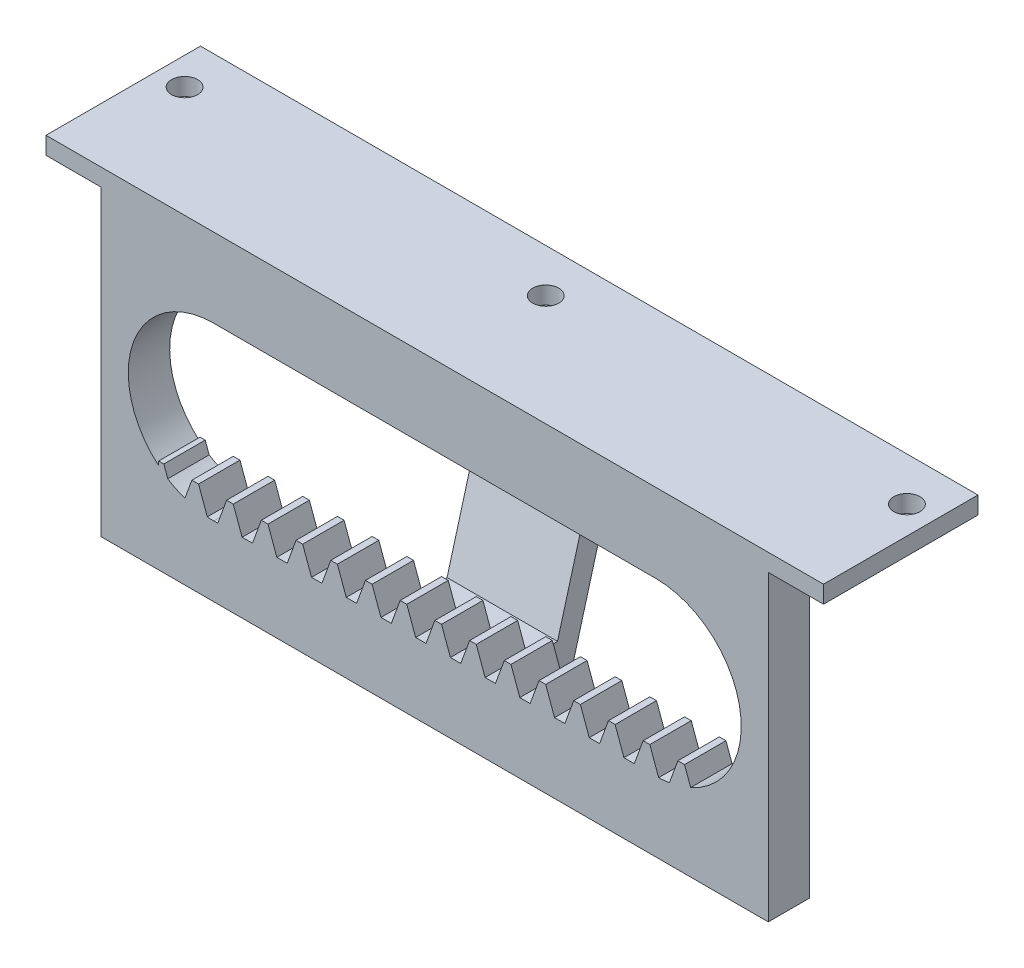
SolidWorks part; units mm, degrees
material "Nylon 101"
ref_plane "Front Plane" through (0, 0, 0) normal (0, 0, 1) x (1, 0, 0)
ref_plane "Top Plane" through (0, 0, 0) normal (0, 1, 0) x (1, 0, 0)
ref_plane "Right Plane" through (0, 0, 0) normal (1, 0, 0) x (0, 0, -1)
sketch "Sketch1" plane through (0, 0, 0) normal (0, 1, 0) x (1, 0, 0)
  line L0 (0, 0) -> (0, 4.7625)
  line L1 (0, 4.7625) -> (63.5, 4.7625)
  line L2 (63.5, 4.7625) -> (63.5, 0)
  line L3 (63.5, 0) -> (0, 0)
  dimension "D1" = 4.7625
  dimension "D2" = 63.5
extrude "Boss-Extrude1" add sketch "Sketch1" along normal blind 4.5
sketch "Sketch2" plane through (0, 0, 0) normal (0, 0, 1) x (1, 0, 0)
  line L0 (0, 3.2275) -> (63.5, 3.2275) construction
  line L1 (0, 4.5) -> (0, 0) construction
  line L2 (63.5, 4.5) -> (63.5, 0) construction
  line L3 (0, 1.7035) -> (63.5, 1.7035) construction
  line L4 (0, 4.5) -> (63.5, 4.5) construction
  line L5 (0, 4.5) -> (0.5952, 4.5) construction
  line L6 (0.5952, 4.5) -> (1.613, 1.7035)
  line L7 (1.613, 1.7035) -> (2.2082, 1.7035)
  line L8 (2.8034, 1.7035) -> (3.8212, 4.5)
  line L9 (3.8212, 4.5) -> (4.4164, 4.5) construction
  line L10 (2.2082, 1.7035) -> (2.8034, 1.7035)
  line L11 (0.5952, 4.5) -> (3.8212, 4.5)
  line L12 (4.5868, 4.5) -> (5.6047, 1.7035)
  line L13 (5.6047, 1.7035) -> (6.1999, 1.7035)
  line L14 (6.795, 1.7035) -> (7.8129, 4.5)
  line L15 (6.1999, 1.7035) -> (6.795, 1.7035)
  line L16 (4.5868, 4.5) -> (7.8129, 4.5)
  line L17 (3.9917, 4.5) -> (4.5868, 4.5) construction
  line L18 (7.8129, 4.5) -> (8.4081, 4.5) construction
  line L19 (8.5785, 4.5) -> (9.5964, 1.7035)
  line L20 (9.5964, 1.7035) -> (10.1915, 1.7035)
  line L21 (10.7867, 1.7035) -> (11.8046, 4.5)
  line L22 (10.1915, 1.7035) -> (10.7867, 1.7035)
  line L23 (8.5785, 4.5) -> (11.8046, 4.5)
  line L24 (7.9834, 4.5) -> (8.5785, 4.5) construction
  line L25 (11.8046, 4.5) -> (12.3997, 4.5) construction
  line L26 (12.5702, 4.5) -> (13.5881, 1.7035)
  line L27 (13.5881, 1.7035) -> (14.1832, 1.7035)
  line L28 (14.7784, 1.7035) -> (15.7962, 4.5)
  line L29 (14.1832, 1.7035) -> (14.7784, 1.7035)
  line L30 (12.5702, 4.5) -> (15.7962, 4.5)
  line L31 (11.975, 4.5) -> (12.5702, 4.5) construction
  line L32 (15.7962, 4.5) -> (16.3914, 4.5) construction
  line L33 (16.5619, 4.5) -> (17.5797, 1.7035)
  line L34 (17.5797, 1.7035) -> (18.1749, 1.7035)
  line L35 (18.7701, 1.7035) -> (19.7879, 4.5)
  line L36 (18.1749, 1.7035) -> (18.7701, 1.7035)
  line L37 (16.5619, 4.5) -> (19.7879, 4.5)
  line L38 (15.9667, 4.5) -> (16.5619, 4.5) construction
  line L39 (19.7879, 4.5) -> (20.3831, 4.5) construction
  line L40 (20.5535, 4.5) -> (21.5714, 1.7035)
  line L41 (21.5714, 1.7035) -> (22.1666, 1.7035)
  line L42 (22.7617, 1.7035) -> (23.7796, 4.5)
  line L43 (22.1666, 1.7035) -> (22.7617, 1.7035)
  line L44 (20.5535, 4.5) -> (23.7796, 4.5)
  line L45 (19.9584, 4.5) -> (20.5535, 4.5) construction
  line L46 (23.7796, 4.5) -> (24.3748, 4.5) construction
  line L47 (24.5452, 4.5) -> (25.5631, 1.7035)
  line L48 (25.5631, 1.7035) -> (26.1582, 1.7035)
  line L49 (26.7534, 1.7035) -> (27.7713, 4.5)
  line L50 (26.1582, 1.7035) -> (26.7534, 1.7035)
  line L51 (24.5452, 4.5) -> (27.7713, 4.5)
  line L52 (23.9501, 4.5) -> (24.5452, 4.5) construction
  line L53 (27.7713, 4.5) -> (28.3664, 4.5) construction
  line L54 (28.5369, 4.5) -> (29.5548, 1.7035)
  line L55 (29.5548, 1.7035) -> (30.1499, 1.7035)
  line L56 (30.7451, 1.7035) -> (31.763, 4.5)
  line L57 (30.1499, 1.7035) -> (30.7451, 1.7035)
  line L58 (28.5369, 4.5) -> (31.763, 4.5)
  line L59 (27.9417, 4.5) -> (28.5369, 4.5) construction
  line L60 (31.763, 4.5) -> (32.3581, 4.5) construction
  line L61 (32.5286, 4.5) -> (33.5464, 1.7035)
  line L62 (33.5464, 1.7035) -> (34.1416, 1.7035)
  line L63 (34.7368, 1.7035) -> (35.7546, 4.5)
  line L64 (34.1416, 1.7035) -> (34.7368, 1.7035)
  line L65 (32.5286, 4.5) -> (35.7546, 4.5)
  line L66 (31.9334, 4.5) -> (32.5286, 4.5) construction
  line L67 (35.7546, 4.5) -> (36.3498, 4.5) construction
  line L68 (36.5203, 4.5) -> (37.5381, 1.7035)
  line L69 (37.5381, 1.7035) -> (38.1333, 1.7035)
  line L70 (38.7284, 1.7035) -> (39.7463, 4.5)
  line L71 (38.1333, 1.7035) -> (38.7284, 1.7035)
  line L72 (36.5203, 4.5) -> (39.7463, 4.5)
  line L73 (35.9251, 4.5) -> (36.5203, 4.5) construction
  line L74 (39.7463, 4.5) -> (40.3415, 4.5) construction
  line L75 (40.5119, 4.5) -> (41.5298, 1.7035)
  line L76 (41.5298, 1.7035) -> (42.125, 1.7035)
  line L77 (42.7201, 1.7035) -> (43.738, 4.5)
  line L78 (42.125, 1.7035) -> (42.7201, 1.7035)
  line L79 (40.5119, 4.5) -> (43.738, 4.5)
  line L80 (39.9168, 4.5) -> (40.5119, 4.5) construction
  line L81 (43.738, 4.5) -> (44.3331, 4.5) construction
  line L82 (44.5036, 4.5) -> (45.5215, 1.7035)
  line L83 (45.5215, 1.7035) -> (46.1166, 1.7035)
  line L84 (46.7118, 1.7035) -> (47.7297, 4.5)
  line L85 (46.1166, 1.7035) -> (46.7118, 1.7035)
  line L86 (44.5036, 4.5) -> (47.7297, 4.5)
  line L87 (43.9084, 4.5) -> (44.5036, 4.5) construction
  line L88 (47.7297, 4.5) -> (48.3248, 4.5) construction
  line L89 (48.4953, 4.5) -> (49.5131, 1.7035)
  line L90 (49.5131, 1.7035) -> (50.1083, 1.7035)
  line L91 (50.7035, 1.7035) -> (51.7213, 4.5)
  line L92 (50.1083, 1.7035) -> (50.7035, 1.7035)
  line L93 (48.4953, 4.5) -> (51.7213, 4.5)
  line L94 (47.9001, 4.5) -> (48.4953, 4.5) construction
  line L95 (51.7213, 4.5) -> (52.3165, 4.5) construction
  line L96 (52.487, 4.5) -> (53.5048, 1.7035)
  line L97 (53.5048, 1.7035) -> (54.1, 1.7035)
  line L98 (54.6952, 1.7035) -> (55.713, 4.5)
  line L99 (54.1, 1.7035) -> (54.6952, 1.7035)
  line L100 (52.487, 4.5) -> (55.713, 4.5)
  line L101 (51.8918, 4.5) -> (52.487, 4.5) construction
  line L102 (55.713, 4.5) -> (56.3082, 4.5) construction
  line L103 (56.4786, 4.5) -> (57.4965, 1.7035)
  line L104 (57.4965, 1.7035) -> (58.0917, 1.7035)
  line L105 (58.6868, 1.7035) -> (59.7047, 4.5)
  line L106 (58.0917, 1.7035) -> (58.6868, 1.7035)
  line L107 (56.4786, 4.5) -> (59.7047, 4.5)
  line L108 (55.8835, 4.5) -> (56.4786, 4.5) construction
  line L109 (59.7047, 4.5) -> (60.2999, 4.5) construction
  line L110 (60.4703, 4.5) -> (61.4882, 1.7035)
  line L111 (61.4882, 1.7035) -> (62.0833, 1.7035)
  line L112 (62.6785, 1.7035) -> (63.6964, 4.5)
  line L113 (62.0833, 1.7035) -> (62.6785, 1.7035)
  line L114 (60.4703, 4.5) -> (63.6964, 4.5)
  line L115 (59.8751, 4.5) -> (60.4703, 4.5) construction
  line L116 (63.6964, 4.5) -> (64.2915, 4.5) construction
  line L117 (64.462, 4.5) -> (65.4798, 1.7035)
  line L118 (65.4798, 1.7035) -> (66.075, 1.7035)
  line L119 (66.6702, 1.7035) -> (67.688, 4.5)
  line L120 (66.075, 1.7035) -> (66.6702, 1.7035)
  line L121 (64.462, 4.5) -> (67.688, 4.5)
  line L122 (63.8668, 4.5) -> (64.462, 4.5) construction
  line L123 (67.688, 4.5) -> (68.2832, 4.5) construction
  line L124 (68.4537, 4.5) -> (69.4715, 1.7035)
  line L125 (69.4715, 1.7035) -> (70.0667, 1.7035)
  line L126 (70.6619, 1.7035) -> (71.6797, 4.5)
  line L127 (70.0667, 1.7035) -> (70.6619, 1.7035)
  line L128 (68.4537, 4.5) -> (71.6797, 4.5)
  line L129 (67.8585, 4.5) -> (68.4537, 4.5) construction
  line L130 (71.6797, 4.5) -> (72.2749, 4.5) construction
  line L131 (72.4453, 4.5) -> (73.4632, 1.7035)
  line L132 (73.4632, 1.7035) -> (74.0584, 1.7035)
  line L133 (74.6535, 1.7035) -> (75.6714, 4.5)
  line L134 (74.0584, 1.7035) -> (74.6535, 1.7035)
  line L135 (72.4453, 4.5) -> (75.6714, 4.5)
  line L136 (71.8502, 4.5) -> (72.4453, 4.5) construction
  line L137 (75.6714, 4.5) -> (76.2666, 4.5) construction
  line L138 (76.437, 4.5) -> (77.4549, 1.7035)
  line L139 (77.4549, 1.7035) -> (78.05, 1.7035)
  line L140 (78.6452, 1.7035) -> (79.6631, 4.5)
  line L141 (78.05, 1.7035) -> (78.6452, 1.7035)
  line L142 (76.437, 4.5) -> (79.6631, 4.5)
  line L143 (75.8418, 4.5) -> (76.437, 4.5) construction
  line L144 (79.6631, 4.5) -> (80.2582, 4.5) construction
  line L145 (80.4287, 4.5) -> (81.4465, 1.7035)
  line L146 (81.4465, 1.7035) -> (82.0417, 1.7035)
  line L147 (82.6369, 1.7035) -> (83.6547, 4.5)
  line L148 (82.0417, 1.7035) -> (82.6369, 1.7035)
  line L149 (80.4287, 4.5) -> (83.6547, 4.5)
  line L150 (79.8335, 4.5) -> (80.4287, 4.5) construction
  line L151 (83.6547, 4.5) -> (84.2499, 4.5) construction
  line L152 (84.4204, 4.5) -> (85.4382, 1.7035)
  line L153 (85.4382, 1.7035) -> (86.0334, 1.7035)
  line L154 (86.6286, 1.7035) -> (87.6464, 4.5)
  line L155 (86.0334, 1.7035) -> (86.6286, 1.7035)
  line L156 (84.4204, 4.5) -> (87.6464, 4.5)
  line L157 (83.8252, 4.5) -> (84.4204, 4.5) construction
  line L158 (87.6464, 4.5) -> (88.2416, 4.5) construction
  line L159 (88.412, 4.5) -> (89.4299, 1.7035)
  line L160 (89.4299, 1.7035) -> (90.0251, 1.7035)
  line L161 (90.6202, 1.7035) -> (91.6381, 4.5)
  line L162 (90.0251, 1.7035) -> (90.6202, 1.7035)
  line L163 (88.412, 4.5) -> (91.6381, 4.5)
  line L164 (87.8169, 4.5) -> (88.412, 4.5) construction
  line L165 (91.6381, 4.5) -> (92.2333, 4.5) construction
  line L166 (92.4037, 4.5) -> (93.4216, 1.7035)
  line L167 (93.4216, 1.7035) -> (94.0167, 1.7035)
  line L168 (94.6119, 1.7035) -> (95.6298, 4.5)
  line L169 (94.0167, 1.7035) -> (94.6119, 1.7035)
  line L170 (92.4037, 4.5) -> (95.6298, 4.5)
  line L171 (91.8086, 4.5) -> (92.4037, 4.5) construction
  line L172 (95.6298, 4.5) -> (96.2249, 4.5) construction
  line L173 (96.3954, 4.5) -> (97.4133, 1.7035)
  line L174 (97.4133, 1.7035) -> (98.0084, 1.7035)
  line L175 (98.6036, 1.7035) -> (99.6214, 4.5)
  line L176 (98.0084, 1.7035) -> (98.6036, 1.7035)
  line L177 (96.3954, 4.5) -> (99.6214, 4.5)
  line L178 (95.8002, 4.5) -> (96.3954, 4.5) construction
  line L179 (99.6214, 4.5) -> (100.2166, 4.5) construction
  line L180 (100.3871, 4.5) -> (101.4049, 1.7035)
  line L181 (101.4049, 1.7035) -> (102.0001, 1.7035)
  line L182 (102.5953, 1.7035) -> (103.6131, 4.5)
  line L183 (102.0001, 1.7035) -> (102.5953, 1.7035)
  line L184 (100.3871, 4.5) -> (103.6131, 4.5)
  line L185 (99.7919, 4.5) -> (100.3871, 4.5) construction
  line L186 (103.6131, 4.5) -> (104.2083, 4.5) construction
  line L187 (104.3787, 4.5) -> (105.3966, 1.7035)
  line L188 (105.3966, 1.7035) -> (105.9918, 1.7035)
  line L189 (106.5869, 1.7035) -> (107.6048, 4.5)
  line L190 (105.9918, 1.7035) -> (106.5869, 1.7035)
  line L191 (104.3787, 4.5) -> (107.6048, 4.5)
  line L192 (103.7836, 4.5) -> (104.3787, 4.5) construction
  line L193 (107.6048, 4.5) -> (108.2, 4.5) construction
  line L194 (108.3704, 4.5) -> (109.3883, 1.7035)
  line L195 (109.3883, 1.7035) -> (109.9835, 1.7035)
  line L196 (110.5786, 1.7035) -> (111.5965, 4.5)
  line L197 (109.9835, 1.7035) -> (110.5786, 1.7035)
  line L198 (108.3704, 4.5) -> (111.5965, 4.5)
  line L199 (107.7753, 4.5) -> (108.3704, 4.5) construction
  line L200 (111.5965, 4.5) -> (112.1916, 4.5) construction
  line L201 (112.3621, 4.5) -> (113.38, 1.7035)
  line L202 (113.38, 1.7035) -> (113.9751, 1.7035)
  line L203 (114.5703, 1.7035) -> (115.5882, 4.5)
  line L204 (113.9751, 1.7035) -> (114.5703, 1.7035)
  line L205 (112.3621, 4.5) -> (115.5882, 4.5)
  line L206 (111.7669, 4.5) -> (112.3621, 4.5) construction
  line L207 (115.5882, 4.5) -> (116.1833, 4.5) construction
  line L208 (116.3538, 4.5) -> (117.3716, 1.7035)
  line L209 (117.3716, 1.7035) -> (117.9668, 1.7035)
  line L210 (118.562, 1.7035) -> (119.5798, 4.5)
  line L211 (117.9668, 1.7035) -> (118.562, 1.7035)
  line L212 (116.3538, 4.5) -> (119.5798, 4.5)
  line L213 (115.7586, 4.5) -> (116.3538, 4.5) construction
  line L214 (119.5798, 4.5) -> (120.175, 4.5) construction
  line L215 (120.3455, 4.5) -> (121.3633, 1.7035)
  line L216 (121.3633, 1.7035) -> (121.9585, 1.7035)
  line L217 (122.5536, 1.7035) -> (123.5715, 4.5)
  line L218 (121.9585, 1.7035) -> (122.5536, 1.7035)
  line L219 (120.3455, 4.5) -> (123.5715, 4.5)
  line L220 (119.7503, 4.5) -> (120.3455, 4.5) construction
  line L221 (123.5715, 4.5) -> (124.1667, 4.5) construction
  line L222 (124.3371, 4.5) -> (125.355, 1.7035)
  line L223 (125.355, 1.7035) -> (125.9502, 1.7035)
  line L224 (126.5453, 1.7035) -> (127.5632, 4.5)
  line L225 (125.9502, 1.7035) -> (126.5453, 1.7035)
  line L226 (124.3371, 4.5) -> (127.5632, 4.5)
  line L227 (123.742, 4.5) -> (124.3371, 4.5) construction
  line L228 (127.5632, 4.5) -> (128.1583, 4.5) construction
  line L229 (128.3288, 4.5) -> (129.3467, 1.7035)
  line L230 (129.3467, 1.7035) -> (129.9418, 1.7035)
  line L231 (130.537, 1.7035) -> (131.5549, 4.5)
  line L232 (129.9418, 1.7035) -> (130.537, 1.7035)
  line L233 (128.3288, 4.5) -> (131.5549, 4.5)
  line L234 (127.7336, 4.5) -> (128.3288, 4.5) construction
  line L235 (131.5549, 4.5) -> (132.15, 4.5) construction
  line L236 (132.3205, 4.5) -> (133.3383, 1.7035)
  line L237 (133.3383, 1.7035) -> (133.9335, 1.7035)
  line L238 (134.5287, 1.7035) -> (135.5465, 4.5)
  line L239 (133.9335, 1.7035) -> (134.5287, 1.7035)
  line L240 (132.3205, 4.5) -> (135.5465, 4.5)
  line L241 (131.7253, 4.5) -> (132.3205, 4.5) construction
  line L242 (135.5465, 4.5) -> (136.1417, 4.5) construction
  line L243 (136.3122, 4.5) -> (137.33, 1.7035)
  line L244 (137.33, 1.7035) -> (137.9252, 1.7035)
  line L245 (138.5204, 1.7035) -> (139.5382, 4.5)
  line L246 (137.9252, 1.7035) -> (138.5204, 1.7035)
  line L247 (136.3122, 4.5) -> (139.5382, 4.5)
  line L248 (135.717, 4.5) -> (136.3122, 4.5) construction
  line L249 (139.5382, 4.5) -> (140.1334, 4.5) construction
  line L250 (140.3038, 4.5) -> (141.3217, 1.7035)
  line L251 (141.3217, 1.7035) -> (141.9169, 1.7035)
  line L252 (142.512, 1.7035) -> (143.5299, 4.5)
  line L253 (141.9169, 1.7035) -> (142.512, 1.7035)
  line L254 (140.3038, 4.5) -> (143.5299, 4.5)
  line L255 (139.7087, 4.5) -> (140.3038, 4.5) construction
  line L256 (143.5299, 4.5) -> (144.1251, 4.5) construction
  line L257 (144.2955, 4.5) -> (145.3134, 1.7035)
  line L258 (145.3134, 1.7035) -> (145.9085, 1.7035)
  line L259 (146.5037, 1.7035) -> (147.5216, 4.5)
  line L260 (145.9085, 1.7035) -> (146.5037, 1.7035)
  line L261 (144.2955, 4.5) -> (147.5216, 4.5)
  line L262 (143.7003, 4.5) -> (144.2955, 4.5) construction
  line L263 (147.5216, 4.5) -> (148.1167, 4.5) construction
  line L264 (148.2872, 4.5) -> (149.305, 1.7035)
  line L265 (149.305, 1.7035) -> (149.9002, 1.7035)
  line L266 (150.4954, 1.7035) -> (151.5132, 4.5)
  line L267 (149.9002, 1.7035) -> (150.4954, 1.7035)
  line L268 (148.2872, 4.5) -> (151.5132, 4.5)
  line L269 (147.692, 4.5) -> (148.2872, 4.5) construction
  line L270 (151.5132, 4.5) -> (152.1084, 4.5) construction
  line L271 (152.2789, 4.5) -> (153.2967, 1.7035)
  line L272 (153.2967, 1.7035) -> (153.8919, 1.7035)
  line L273 (154.4871, 1.7035) -> (155.5049, 4.5)
  line L274 (153.8919, 1.7035) -> (154.4871, 1.7035)
  line L275 (152.2789, 4.5) -> (155.5049, 4.5)
  line L276 (151.6837, 4.5) -> (152.2789, 4.5) construction
  line L277 (155.5049, 4.5) -> (156.1001, 4.5) construction
  line L278 (156.2705, 4.5) -> (157.2884, 1.7035)
  line L279 (157.2884, 1.7035) -> (157.8836, 1.7035)
  line L280 (158.4787, 1.7035) -> (159.4966, 4.5)
  line L281 (157.8836, 1.7035) -> (158.4787, 1.7035)
  line L282 (156.2705, 4.5) -> (159.4966, 4.5)
  line L283 (155.6754, 4.5) -> (156.2705, 4.5) construction
  line L284 (159.4966, 4.5) -> (160.0918, 4.5) construction
  line L285 (160.2622, 4.5) -> (161.2801, 1.7035)
  line L286 (161.2801, 1.7035) -> (161.8752, 1.7035)
  line L287 (162.4704, 1.7035) -> (163.4883, 4.5)
  line L288 (161.8752, 1.7035) -> (162.4704, 1.7035)
  line L289 (160.2622, 4.5) -> (163.4883, 4.5)
  line L290 (159.667, 4.5) -> (160.2622, 4.5) construction
  line L291 (163.4883, 4.5) -> (164.0834, 4.5) construction
  line L292 (164.2539, 4.5) -> (165.2718, 1.7035)
  line L293 (165.2718, 1.7035) -> (165.8669, 1.7035)
  line L294 (166.4621, 1.7035) -> (167.4799, 4.5)
  line L295 (165.8669, 1.7035) -> (166.4621, 1.7035)
  line L296 (164.2539, 4.5) -> (167.4799, 4.5)
  line L297 (163.6587, 4.5) -> (164.2539, 4.5) construction
  line L298 (167.4799, 4.5) -> (168.0751, 4.5) construction
  line L299 (168.2456, 4.5) -> (169.2634, 1.7035)
  line L300 (169.2634, 1.7035) -> (169.8586, 1.7035)
  line L301 (170.4538, 1.7035) -> (171.4716, 4.5)
  line L302 (169.8586, 1.7035) -> (170.4538, 1.7035)
  line L303 (168.2456, 4.5) -> (171.4716, 4.5)
  line L304 (167.6504, 4.5) -> (168.2456, 4.5) construction
  line L305 (171.4716, 4.5) -> (172.0668, 4.5) construction
  line L306 (172.2372, 4.5) -> (173.2551, 1.7035)
  line L307 (173.2551, 1.7035) -> (173.8503, 1.7035)
  line L308 (174.4454, 1.7035) -> (175.4633, 4.5)
  line L309 (173.8503, 1.7035) -> (174.4454, 1.7035)
  line L310 (172.2372, 4.5) -> (175.4633, 4.5)
  line L311 (171.6421, 4.5) -> (172.2372, 4.5) construction
  line L312 (175.4633, 4.5) -> (176.0585, 4.5) construction
  line L313 (176.2289, 4.5) -> (177.2468, 1.7035)
  line L314 (177.2468, 1.7035) -> (177.8419, 1.7035)
  line L315 (178.4371, 1.7035) -> (179.455, 4.5)
  line L316 (177.8419, 1.7035) -> (178.4371, 1.7035)
  line L317 (176.2289, 4.5) -> (179.455, 4.5)
  line L318 (175.6338, 4.5) -> (176.2289, 4.5) construction
  line L319 (179.455, 4.5) -> (180.0501, 4.5) construction
  line L320 (180.2206, 4.5) -> (181.2385, 1.7035)
  line L321 (181.2385, 1.7035) -> (181.8336, 1.7035)
  line L322 (182.4288, 1.7035) -> (183.4466, 4.5)
  line L323 (181.8336, 1.7035) -> (182.4288, 1.7035)
  line L324 (180.2206, 4.5) -> (183.4466, 4.5)
  line L325 (179.6254, 4.5) -> (180.2206, 4.5) construction
  line L326 (183.4466, 4.5) -> (184.0418, 4.5) construction
  line L327 (184.2123, 4.5) -> (185.2301, 1.7035)
  line L328 (185.2301, 1.7035) -> (185.8253, 1.7035)
  line L329 (186.4205, 1.7035) -> (187.4383, 4.5)
  line L330 (185.8253, 1.7035) -> (186.4205, 1.7035)
  line L331 (184.2123, 4.5) -> (187.4383, 4.5)
  line L332 (183.6171, 4.5) -> (184.2123, 4.5) construction
  line L333 (187.4383, 4.5) -> (188.0335, 4.5) construction
  line L334 (188.204, 4.5) -> (189.2218, 1.7035)
  line L335 (189.2218, 1.7035) -> (189.817, 1.7035)
  line L336 (190.4121, 1.7035) -> (191.43, 4.5)
  line L337 (189.817, 1.7035) -> (190.4121, 1.7035)
  line L338 (188.204, 4.5) -> (191.43, 4.5)
  line L339 (187.6088, 4.5) -> (188.204, 4.5) construction
  line L340 (191.43, 4.5) -> (192.0252, 4.5) construction
  line L341 (192.1956, 4.5) -> (193.2135, 1.7035)
  line L342 (193.2135, 1.7035) -> (193.8087, 1.7035)
  line L343 (194.4038, 1.7035) -> (195.4217, 4.5)
  line L344 (193.8087, 1.7035) -> (194.4038, 1.7035)
  line L345 (192.1956, 4.5) -> (195.4217, 4.5)
  line L346 (191.6005, 4.5) -> (192.1956, 4.5) construction
  line L347 (195.4217, 4.5) -> (196.0168, 4.5) construction
  line L348 (196.1873, 4.5) -> (197.2052, 1.7035)
  line L349 (197.2052, 1.7035) -> (197.8003, 1.7035)
  line L350 (198.3955, 1.7035) -> (199.4134, 4.5)
  line L351 (197.8003, 1.7035) -> (198.3955, 1.7035)
  line L352 (196.1873, 4.5) -> (199.4134, 4.5)
  line L353 (195.5921, 4.5) -> (196.1873, 4.5) construction
  line L354 (199.4134, 4.5) -> (200.0085, 4.5) construction
  line L355 (200.179, 4.5) -> (201.1968, 1.7035)
  line L356 (201.1968, 1.7035) -> (201.792, 1.7035)
  line L357 (202.3872, 1.7035) -> (203.405, 4.5)
  line L358 (201.792, 1.7035) -> (202.3872, 1.7035)
  line L359 (200.179, 4.5) -> (203.405, 4.5)
  line L360 (199.5838, 4.5) -> (200.179, 4.5) construction
  line L361 (203.405, 4.5) -> (204.0002, 4.5) construction
  line L362 (204.1707, 4.5) -> (205.1885, 1.7035)
  line L363 (205.1885, 1.7035) -> (205.7837, 1.7035)
  line L364 (206.3788, 1.7035) -> (207.3967, 4.5)
  line L365 (205.7837, 1.7035) -> (206.3788, 1.7035)
  line L366 (204.1707, 4.5) -> (207.3967, 4.5)
  line L367 (203.5755, 4.5) -> (204.1707, 4.5) construction
  line L368 (207.3967, 4.5) -> (207.9919, 4.5) construction
  line L369 (208.1623, 4.5) -> (209.1802, 1.7035)
  line L370 (209.1802, 1.7035) -> (209.7754, 1.7035)
  line L371 (210.3705, 1.7035) -> (211.3884, 4.5)
  line L372 (209.7754, 1.7035) -> (210.3705, 1.7035)
  line L373 (208.1623, 4.5) -> (211.3884, 4.5)
  line L374 (207.5672, 4.5) -> (208.1623, 4.5) construction
  line L375 (211.3884, 4.5) -> (211.9835, 4.5) construction
  line L376 (212.154, 4.5) -> (213.1719, 1.7035)
  line L377 (213.1719, 1.7035) -> (213.767, 1.7035)
  line L378 (214.3622, 1.7035) -> (215.3801, 4.5)
  line L379 (213.767, 1.7035) -> (214.3622, 1.7035)
  line L380 (212.154, 4.5) -> (215.3801, 4.5)
  line L381 (211.5588, 4.5) -> (212.154, 4.5) construction
  line L382 (215.3801, 4.5) -> (215.9752, 4.5) construction
  line L383 (216.1457, 4.5) -> (217.1635, 1.7035)
  line L384 (217.1635, 1.7035) -> (217.7587, 1.7035)
  line L385 (218.3539, 1.7035) -> (219.3717, 4.5)
  line L386 (217.7587, 1.7035) -> (218.3539, 1.7035)
  line L387 (216.1457, 4.5) -> (219.3717, 4.5)
  line L388 (215.5505, 4.5) -> (216.1457, 4.5) construction
  line L389 (219.3717, 4.5) -> (219.9669, 4.5) construction
  line L390 (220.1374, 4.5) -> (221.1552, 1.7035)
  line L391 (221.1552, 1.7035) -> (221.7504, 1.7035)
  line L392 (222.3456, 1.7035) -> (223.3634, 4.5)
  line L393 (221.7504, 1.7035) -> (222.3456, 1.7035)
  line L394 (220.1374, 4.5) -> (223.3634, 4.5)
  line L395 (219.5422, 4.5) -> (220.1374, 4.5) construction
  line L396 (223.3634, 4.5) -> (223.9586, 4.5) construction
  line L397 (224.129, 4.5) -> (225.1469, 1.7035)
  line L398 (225.1469, 1.7035) -> (225.7421, 1.7035)
  line L399 (226.3372, 1.7035) -> (227.3551, 4.5)
  line L400 (225.7421, 1.7035) -> (226.3372, 1.7035)
  line L401 (224.129, 4.5) -> (227.3551, 4.5)
  line L402 (223.5339, 4.5) -> (224.129, 4.5) construction
  line L403 (227.3551, 4.5) -> (227.9503, 4.5) construction
  line L404 (228.1207, 4.5) -> (229.1386, 1.7035)
  line L405 (229.1386, 1.7035) -> (229.7337, 1.7035)
  line L406 (230.3289, 1.7035) -> (231.3468, 4.5)
  line L407 (229.7337, 1.7035) -> (230.3289, 1.7035)
  line L408 (228.1207, 4.5) -> (231.3468, 4.5)
  line L409 (227.5255, 4.5) -> (228.1207, 4.5) construction
  line L410 (231.3468, 4.5) -> (231.9419, 4.5) construction
  line L411 (232.1124, 4.5) -> (233.1302, 1.7035)
  line L412 (233.1302, 1.7035) -> (233.7254, 1.7035)
  line L413 (234.3206, 1.7035) -> (235.3384, 4.5)
  line L414 (233.7254, 1.7035) -> (234.3206, 1.7035)
  line L415 (232.1124, 4.5) -> (235.3384, 4.5)
  line L416 (231.5172, 4.5) -> (232.1124, 4.5) construction
  line L417 (235.3384, 4.5) -> (235.9336, 4.5) construction
  line L418 (236.1041, 4.5) -> (237.1219, 1.7035)
  line L419 (237.1219, 1.7035) -> (237.7171, 1.7035)
  line L420 (238.3123, 1.7035) -> (239.3301, 4.5)
  line L421 (237.7171, 1.7035) -> (238.3123, 1.7035)
  line L422 (236.1041, 4.5) -> (239.3301, 4.5)
  line L423 (235.5089, 4.5) -> (236.1041, 4.5) construction
  line L424 (239.3301, 4.5) -> (239.9253, 4.5) construction
  line L425 (240.0957, 4.5) -> (241.1136, 1.7035)
  line L426 (241.1136, 1.7035) -> (241.7088, 1.7035)
  line L427 (242.3039, 1.7035) -> (243.3218, 4.5)
  line L428 (241.7088, 1.7035) -> (242.3039, 1.7035)
  line L429 (240.0957, 4.5) -> (243.3218, 4.5)
  line L430 (239.5006, 4.5) -> (240.0957, 4.5) construction
  line L431 (243.3218, 4.5) -> (243.917, 4.5) construction
  line L432 (244.0874, 4.5) -> (245.1053, 1.7035)
  line L433 (245.1053, 1.7035) -> (245.7004, 1.7035)
  line L434 (246.2956, 1.7035) -> (247.3135, 4.5)
  line L435 (245.7004, 1.7035) -> (246.2956, 1.7035)
  line L436 (244.0874, 4.5) -> (247.3135, 4.5)
  line L437 (243.4923, 4.5) -> (244.0874, 4.5) construction
  line L438 (247.3135, 4.5) -> (247.9086, 4.5) construction
  line L439 (248.0791, 4.5) -> (249.097, 1.7035)
  line L440 (249.097, 1.7035) -> (249.6921, 1.7035)
  line L441 (250.2873, 1.7035) -> (251.3051, 4.5)
  line L442 (249.6921, 1.7035) -> (250.2873, 1.7035)
  line L443 (248.0791, 4.5) -> (251.3051, 4.5)
  line L444 (247.4839, 4.5) -> (248.0791, 4.5) construction
  line L445 (251.3051, 4.5) -> (251.9003, 4.5) construction
  line L446 (252.0708, 4.5) -> (253.0886, 1.7035)
  line L447 (253.0886, 1.7035) -> (253.6838, 1.7035)
  line L448 (254.279, 1.7035) -> (255.2968, 4.5)
  line L449 (253.6838, 1.7035) -> (254.279, 1.7035)
  line L450 (252.0708, 4.5) -> (255.2968, 4.5)
  line L451 (251.4756, 4.5) -> (252.0708, 4.5) construction
  line L452 (255.2968, 4.5) -> (255.892, 4.5) construction
  line L453 (256.0624, 4.5) -> (257.0803, 1.7035)
  line L454 (257.0803, 1.7035) -> (257.6755, 1.7035)
  line L455 (258.2706, 1.7035) -> (259.2885, 4.5)
  line L456 (257.6755, 1.7035) -> (258.2706, 1.7035)
  line L457 (256.0624, 4.5) -> (259.2885, 4.5)
  line L458 (255.4673, 4.5) -> (256.0624, 4.5) construction
  line L459 (259.2885, 4.5) -> (259.8837, 4.5) construction
  line L460 (260.0541, 4.5) -> (261.072, 1.7035)
  line L461 (261.072, 1.7035) -> (261.6671, 1.7035)
  line L462 (262.2623, 1.7035) -> (263.2802, 4.5)
  line L463 (261.6671, 1.7035) -> (262.2623, 1.7035)
  line L464 (260.0541, 4.5) -> (263.2802, 4.5)
  line L465 (259.459, 4.5) -> (260.0541, 4.5) construction
  line L466 (263.2802, 4.5) -> (263.8753, 4.5) construction
  line L467 (264.0458, 4.5) -> (265.0637, 1.7035)
  line L468 (265.0637, 1.7035) -> (265.6588, 1.7035)
  line L469 (266.254, 1.7035) -> (267.2718, 4.5)
  line L470 (265.6588, 1.7035) -> (266.254, 1.7035)
  line L471 (264.0458, 4.5) -> (267.2718, 4.5)
  line L472 (263.4506, 4.5) -> (264.0458, 4.5) construction
  line L473 (267.2718, 4.5) -> (267.867, 4.5) construction
  line L474 (268.0375, 4.5) -> (269.0553, 1.7035)
  line L475 (269.0553, 1.7035) -> (269.6505, 1.7035)
  line L476 (270.2457, 1.7035) -> (271.2635, 4.5)
  line L477 (269.6505, 1.7035) -> (270.2457, 1.7035)
  line L478 (268.0375, 4.5) -> (271.2635, 4.5)
  line L479 (267.4423, 4.5) -> (268.0375, 4.5) construction
  line L480 (271.2635, 4.5) -> (271.8587, 4.5) construction
  line L481 (272.0292, 4.5) -> (273.047, 1.7035)
  line L482 (273.047, 1.7035) -> (273.6422, 1.7035)
  line L483 (274.2373, 1.7035) -> (275.2552, 4.5)
  line L484 (273.6422, 1.7035) -> (274.2373, 1.7035)
  line L485 (272.0292, 4.5) -> (275.2552, 4.5)
  line L486 (271.434, 4.5) -> (272.0292, 4.5) construction
  line L487 (275.2552, 4.5) -> (275.8504, 4.5) construction
  line L488 (276.0208, 4.5) -> (277.0387, 1.7035)
  line L489 (277.0387, 1.7035) -> (277.6339, 1.7035)
  line L490 (278.229, 1.7035) -> (279.2469, 4.5)
  line L491 (277.6339, 1.7035) -> (278.229, 1.7035)
  line L492 (276.0208, 4.5) -> (279.2469, 4.5)
  line L493 (275.4257, 4.5) -> (276.0208, 4.5) construction
  line L494 (279.2469, 4.5) -> (279.842, 4.5) construction
  line L495 (280.0125, 4.5) -> (281.0304, 1.7035)
  line L496 (281.0304, 1.7035) -> (281.6255, 1.7035)
  line L497 (282.2207, 1.7035) -> (283.2386, 4.5)
  line L498 (281.6255, 1.7035) -> (282.2207, 1.7035)
  line L499 (280.0125, 4.5) -> (283.2386, 4.5)
  line L500 (279.4173, 4.5) -> (280.0125, 4.5) construction
  line L501 (283.2386, 4.5) -> (283.8337, 4.5) construction
  line L502 (284.0042, 4.5) -> (285.022, 1.7035)
  line L503 (285.022, 1.7035) -> (285.6172, 1.7035)
  line L504 (286.2124, 1.7035) -> (287.2302, 4.5)
  line L505 (285.6172, 1.7035) -> (286.2124, 1.7035)
  line L506 (284.0042, 4.5) -> (287.2302, 4.5)
  line L507 (283.409, 4.5) -> (284.0042, 4.5) construction
  line L508 (287.2302, 4.5) -> (287.8254, 4.5) construction
  line L509 (287.9959, 4.5) -> (289.0137, 1.7035)
  line L510 (289.0137, 1.7035) -> (289.6089, 1.7035)
  line L511 (290.204, 1.7035) -> (291.2219, 4.5)
  line L512 (289.6089, 1.7035) -> (290.204, 1.7035)
  line L513 (287.9959, 4.5) -> (291.2219, 4.5)
  line L514 (287.4007, 4.5) -> (287.9959, 4.5) construction
  line L515 (291.2219, 4.5) -> (291.8171, 4.5) construction
  line L516 (291.9875, 4.5) -> (293.0054, 1.7035)
  line L517 (293.0054, 1.7035) -> (293.6006, 1.7035)
  line L518 (294.1957, 1.7035) -> (295.2136, 4.5)
  line L519 (293.6006, 1.7035) -> (294.1957, 1.7035)
  line L520 (291.9875, 4.5) -> (295.2136, 4.5)
  line L521 (291.3924, 4.5) -> (291.9875, 4.5) construction
  line L522 (295.2136, 4.5) -> (295.8087, 4.5) construction
  line L523 (295.9792, 4.5) -> (296.9971, 1.7035)
  line L524 (296.9971, 1.7035) -> (297.5922, 1.7035)
  line L525 (298.1874, 1.7035) -> (299.2053, 4.5)
  line L526 (297.5922, 1.7035) -> (298.1874, 1.7035)
  line L527 (295.9792, 4.5) -> (299.2053, 4.5)
  line L528 (295.384, 4.5) -> (295.9792, 4.5) construction
  line L529 (299.2053, 4.5) -> (299.8004, 4.5) construction
  line L530 (299.9709, 4.5) -> (300.9887, 1.7035)
  line L531 (300.9887, 1.7035) -> (301.5839, 1.7035)
  line L532 (302.1791, 1.7035) -> (303.1969, 4.5)
  line L533 (301.5839, 1.7035) -> (302.1791, 1.7035)
  line L534 (299.9709, 4.5) -> (303.1969, 4.5)
  line L535 (299.3757, 4.5) -> (299.9709, 4.5) construction
  line L536 (303.1969, 4.5) -> (303.7921, 4.5) construction
  line L537 (303.9626, 4.5) -> (304.9804, 1.7035)
  line L538 (304.9804, 1.7035) -> (305.5756, 1.7035)
  line L539 (306.1708, 1.7035) -> (307.1886, 4.5)
  line L540 (305.5756, 1.7035) -> (306.1708, 1.7035)
  line L541 (303.9626, 4.5) -> (307.1886, 4.5)
  line L542 (303.3674, 4.5) -> (303.9626, 4.5) construction
  line L543 (307.1886, 4.5) -> (307.7838, 4.5) construction
  line L544 (307.9542, 4.5) -> (308.9721, 1.7035)
  line L545 (308.9721, 1.7035) -> (309.5673, 1.7035)
  line L546 (310.1624, 1.7035) -> (311.1803, 4.5)
  line L547 (309.5673, 1.7035) -> (310.1624, 1.7035)
  line L548 (307.9542, 4.5) -> (311.1803, 4.5)
  line L549 (307.3591, 4.5) -> (307.9542, 4.5) construction
  line L550 (311.1803, 4.5) -> (311.7755, 4.5) construction
  line L551 (311.9459, 4.5) -> (312.9638, 1.7035)
  line L552 (312.9638, 1.7035) -> (313.5589, 1.7035)
  line L553 (314.1541, 1.7035) -> (315.172, 4.5)
  line L554 (313.5589, 1.7035) -> (314.1541, 1.7035)
  line L555 (311.9459, 4.5) -> (315.172, 4.5)
  line L556 (311.3507, 4.5) -> (311.9459, 4.5) construction
  line L557 (315.172, 4.5) -> (315.7671, 4.5) construction
  line L558 (315.9376, 4.5) -> (316.9554, 1.7035)
  line L559 (316.9554, 1.7035) -> (317.5506, 1.7035)
  line L560 (318.1458, 1.7035) -> (319.1636, 4.5)
  line L561 (317.5506, 1.7035) -> (318.1458, 1.7035)
  line L562 (315.9376, 4.5) -> (319.1636, 4.5)
  line L563 (315.3424, 4.5) -> (315.9376, 4.5) construction
  line L564 (319.1636, 4.5) -> (319.7588, 4.5) construction
  line L565 (319.9293, 4.5) -> (320.9471, 1.7035)
  line L566 (320.9471, 1.7035) -> (321.5423, 1.7035)
  line L567 (322.1375, 1.7035) -> (323.1553, 4.5)
  line L568 (321.5423, 1.7035) -> (322.1375, 1.7035)
  line L569 (319.9293, 4.5) -> (323.1553, 4.5)
  line L570 (319.3341, 4.5) -> (319.9293, 4.5) construction
  line L571 (323.1553, 4.5) -> (323.7505, 4.5) construction
  line L572 (323.9209, 4.5) -> (324.9388, 1.7035)
  line L573 (324.9388, 1.7035) -> (325.534, 1.7035)
  line L574 (326.1291, 1.7035) -> (327.147, 4.5)
  line L575 (325.534, 1.7035) -> (326.1291, 1.7035)
  line L576 (323.9209, 4.5) -> (327.147, 4.5)
  line L577 (323.3258, 4.5) -> (323.9209, 4.5) construction
  line L578 (327.147, 4.5) -> (327.7422, 4.5) construction
  line L579 (327.9126, 4.5) -> (328.9305, 1.7035)
  line L580 (328.9305, 1.7035) -> (329.5256, 1.7035)
  line L581 (330.1208, 1.7035) -> (331.1387, 4.5)
  line L582 (329.5256, 1.7035) -> (330.1208, 1.7035)
  line L583 (327.9126, 4.5) -> (331.1387, 4.5)
  line L584 (327.3175, 4.5) -> (327.9126, 4.5) construction
  line L585 (331.1387, 4.5) -> (331.7338, 4.5) construction
  line L586 (331.9043, 4.5) -> (332.9222, 1.7035)
  line L587 (332.9222, 1.7035) -> (333.5173, 1.7035)
  line L588 (334.1125, 1.7035) -> (335.1303, 4.5)
  line L589 (333.5173, 1.7035) -> (334.1125, 1.7035)
  line L590 (331.9043, 4.5) -> (335.1303, 4.5)
  line L591 (331.3091, 4.5) -> (331.9043, 4.5) construction
  line L592 (335.1303, 4.5) -> (335.7255, 4.5) construction
  line L593 (335.896, 4.5) -> (336.9138, 1.7035)
  line L594 (336.9138, 1.7035) -> (337.509, 1.7035)
  line L595 (338.1042, 1.7035) -> (339.122, 4.5)
  line L596 (337.509, 1.7035) -> (338.1042, 1.7035)
  line L597 (335.896, 4.5) -> (339.122, 4.5)
  line L598 (335.3008, 4.5) -> (335.896, 4.5) construction
  line L599 (339.122, 4.5) -> (339.7172, 4.5) construction
  line L600 (339.8876, 4.5) -> (340.9055, 1.7035)
  line L601 (340.9055, 1.7035) -> (341.5007, 1.7035)
  line L602 (342.0958, 1.7035) -> (343.1137, 4.5)
  line L603 (341.5007, 1.7035) -> (342.0958, 1.7035)
  line L604 (339.8876, 4.5) -> (343.1137, 4.5)
  line L605 (339.2925, 4.5) -> (339.8876, 4.5) construction
  line L606 (343.1137, 4.5) -> (343.7089, 4.5) construction
  line L607 (343.8793, 4.5) -> (344.8972, 1.7035)
  line L608 (344.8972, 1.7035) -> (345.4923, 1.7035)
  line L609 (346.0875, 1.7035) -> (347.1054, 4.5)
  line L610 (345.4923, 1.7035) -> (346.0875, 1.7035)
  line L611 (343.8793, 4.5) -> (347.1054, 4.5)
  line L612 (343.2842, 4.5) -> (343.8793, 4.5) construction
  line L613 (347.1054, 4.5) -> (347.7005, 4.5) construction
  line L614 (347.871, 4.5) -> (348.8889, 1.7035)
  line L615 (348.8889, 1.7035) -> (349.484, 1.7035)
  line L616 (350.0792, 1.7035) -> (351.097, 4.5)
  line L617 (349.484, 1.7035) -> (350.0792, 1.7035)
  line L618 (347.871, 4.5) -> (351.097, 4.5)
  line L619 (347.2758, 4.5) -> (347.871, 4.5) construction
  line L620 (351.097, 4.5) -> (351.6922, 4.5) construction
  line L621 (351.8627, 4.5) -> (352.8805, 1.7035)
  line L622 (352.8805, 1.7035) -> (353.4757, 1.7035)
  line L623 (354.0709, 1.7035) -> (355.0887, 4.5)
  line L624 (353.4757, 1.7035) -> (354.0709, 1.7035)
  line L625 (351.8627, 4.5) -> (355.0887, 4.5)
  line L626 (351.2675, 4.5) -> (351.8627, 4.5) construction
  line L627 (355.0887, 4.5) -> (355.6839, 4.5) construction
  line L628 (355.8544, 4.5) -> (356.8722, 1.7035)
  line L629 (356.8722, 1.7035) -> (357.4674, 1.7035)
  line L630 (358.0625, 1.7035) -> (359.0804, 4.5)
  line L631 (357.4674, 1.7035) -> (358.0625, 1.7035)
  line L632 (355.8544, 4.5) -> (359.0804, 4.5)
  line L633 (355.2592, 4.5) -> (355.8544, 4.5) construction
  line L634 (359.0804, 4.5) -> (359.6756, 4.5) construction
  line L635 (359.846, 4.5) -> (360.8639, 1.7035)
  line L636 (360.8639, 1.7035) -> (361.4591, 1.7035)
  line L637 (362.0542, 1.7035) -> (363.0721, 4.5)
  line L638 (361.4591, 1.7035) -> (362.0542, 1.7035)
  line L639 (359.846, 4.5) -> (363.0721, 4.5)
  line L640 (359.2509, 4.5) -> (359.846, 4.5) construction
  line L641 (363.0721, 4.5) -> (363.6672, 4.5) construction
  line L642 (363.8377, 4.5) -> (364.8556, 1.7035)
  line L643 (364.8556, 1.7035) -> (365.4507, 1.7035)
  line L644 (366.0459, 1.7035) -> (367.0638, 4.5)
  line L645 (365.4507, 1.7035) -> (366.0459, 1.7035)
  line L646 (363.8377, 4.5) -> (367.0638, 4.5)
  line L647 (363.2425, 4.5) -> (363.8377, 4.5) construction
  line L648 (367.0638, 4.5) -> (367.6589, 4.5) construction
  line L649 (367.8294, 4.5) -> (368.8472, 1.7035)
  line L650 (368.8472, 1.7035) -> (369.4424, 1.7035)
  line L651 (370.0376, 1.7035) -> (371.0554, 4.5)
  line L652 (369.4424, 1.7035) -> (370.0376, 1.7035)
  line L653 (367.8294, 4.5) -> (371.0554, 4.5)
  line L654 (367.2342, 4.5) -> (367.8294, 4.5) construction
  line L655 (371.0554, 4.5) -> (371.6506, 4.5) construction
  line L656 (371.8211, 4.5) -> (372.8389, 1.7035)
  line L657 (372.8389, 1.7035) -> (373.4341, 1.7035)
  line L658 (374.0292, 1.7035) -> (375.0471, 4.5)
  line L659 (373.4341, 1.7035) -> (374.0292, 1.7035)
  line L660 (371.8211, 4.5) -> (375.0471, 4.5)
  line L661 (371.2259, 4.5) -> (371.8211, 4.5) construction
  line L662 (375.0471, 4.5) -> (375.6423, 4.5) construction
  line L663 (375.8127, 4.5) -> (376.8306, 1.7035)
  line L664 (376.8306, 1.7035) -> (377.4258, 1.7035)
  line L665 (378.0209, 1.7035) -> (379.0388, 4.5)
  line L666 (377.4258, 1.7035) -> (378.0209, 1.7035)
  line L667 (375.8127, 4.5) -> (379.0388, 4.5)
  line L668 (375.2176, 4.5) -> (375.8127, 4.5) construction
  line L669 (379.0388, 4.5) -> (379.6339, 4.5) construction
  line L670 (379.8044, 4.5) -> (380.8223, 1.7035)
  line L671 (380.8223, 1.7035) -> (381.4174, 1.7035)
  line L672 (382.0126, 1.7035) -> (383.0305, 4.5)
  line L673 (381.4174, 1.7035) -> (382.0126, 1.7035)
  line L674 (379.8044, 4.5) -> (383.0305, 4.5)
  line L675 (379.2092, 4.5) -> (379.8044, 4.5) construction
  line L676 (383.0305, 4.5) -> (383.6256, 4.5) construction
  line L677 (383.7961, 4.5) -> (384.8139, 1.7035)
  line L678 (384.8139, 1.7035) -> (385.4091, 1.7035)
  line L679 (386.0043, 1.7035) -> (387.0221, 4.5)
  line L680 (385.4091, 1.7035) -> (386.0043, 1.7035)
  line L681 (383.7961, 4.5) -> (387.0221, 4.5)
  line L682 (383.2009, 4.5) -> (383.7961, 4.5) construction
  line L683 (387.0221, 4.5) -> (387.6173, 4.5) construction
  line L684 (387.7878, 4.5) -> (388.8056, 1.7035)
  line L685 (388.8056, 1.7035) -> (389.4008, 1.7035)
  line L686 (389.996, 1.7035) -> (391.0138, 4.5)
  line L687 (389.4008, 1.7035) -> (389.996, 1.7035)
  line L688 (387.7878, 4.5) -> (391.0138, 4.5)
  line L689 (387.1926, 4.5) -> (387.7878, 4.5) construction
  line L690 (391.0138, 4.5) -> (391.609, 4.5) construction
  line L691 (391.7794, 4.5) -> (392.7973, 1.7035)
  line L692 (392.7973, 1.7035) -> (393.3925, 1.7035)
  line L693 (393.9876, 1.7035) -> (395.0055, 4.5)
  line L694 (393.3925, 1.7035) -> (393.9876, 1.7035)
  line L695 (391.7794, 4.5) -> (395.0055, 4.5)
  line L696 (391.1843, 4.5) -> (391.7794, 4.5) construction
  line L697 (395.0055, 4.5) -> (395.6007, 4.5) construction
  line L698 (395.7711, 4.5) -> (396.789, 1.7035)
  line L699 (396.789, 1.7035) -> (397.3841, 1.7035)
  line L700 (397.9793, 1.7035) -> (398.9972, 4.5)
  line L701 (397.3841, 1.7035) -> (397.9793, 1.7035)
  line L702 (395.7711, 4.5) -> (398.9972, 4.5)
  line L703 (395.1759, 4.5) -> (395.7711, 4.5) construction
  line L704 (398.9972, 4.5) -> (399.5923, 4.5) construction
  line L705 (399.7628, 4.5) -> (400.7806, 1.7035)
  line L706 (400.7806, 1.7035) -> (401.3758, 1.7035)
  line L707 (401.971, 1.7035) -> (402.9888, 4.5)
  line L708 (401.3758, 1.7035) -> (401.971, 1.7035)
  line L709 (399.7628, 4.5) -> (402.9888, 4.5)
  line L710 (399.1676, 4.5) -> (399.7628, 4.5) construction
  line L711 (402.9888, 4.5) -> (403.584, 4.5) construction
  line L712 (403.7545, 4.5) -> (404.7723, 1.7035)
  line L713 (404.7723, 1.7035) -> (405.3675, 1.7035)
  line L714 (405.9627, 1.7035) -> (406.9805, 4.5)
  line L715 (405.3675, 1.7035) -> (405.9627, 1.7035)
  line L716 (403.7545, 4.5) -> (406.9805, 4.5)
  line L717 (403.1593, 4.5) -> (403.7545, 4.5) construction
  line L718 (406.9805, 4.5) -> (407.5757, 4.5) construction
  line L719 (407.7461, 4.5) -> (408.764, 1.7035)
  line L720 (408.764, 1.7035) -> (409.3592, 1.7035)
  line L721 (409.9543, 1.7035) -> (410.9722, 4.5)
  line L722 (409.3592, 1.7035) -> (409.9543, 1.7035)
  line L723 (407.7461, 4.5) -> (410.9722, 4.5)
  line L724 (407.151, 4.5) -> (407.7461, 4.5) construction
  line L725 (410.9722, 4.5) -> (411.5674, 4.5) construction
  line L726 (411.7378, 4.5) -> (412.7557, 1.7035)
  line L727 (412.7557, 1.7035) -> (413.3508, 1.7035)
  line L728 (413.946, 1.7035) -> (414.9639, 4.5)
  line L729 (413.3508, 1.7035) -> (413.946, 1.7035)
  line L730 (411.7378, 4.5) -> (414.9639, 4.5)
  line L731 (411.1427, 4.5) -> (411.7378, 4.5) construction
  line L732 (414.9639, 4.5) -> (415.559, 4.5) construction
  line L733 (415.7295, 4.5) -> (416.7474, 1.7035)
  line L734 (416.7474, 1.7035) -> (417.3425, 1.7035)
  line L735 (417.9377, 1.7035) -> (418.9555, 4.5)
  line L736 (417.3425, 1.7035) -> (417.9377, 1.7035)
  line L737 (415.7295, 4.5) -> (418.9555, 4.5)
  line L738 (415.1343, 4.5) -> (415.7295, 4.5) construction
  line L739 (418.9555, 4.5) -> (419.5507, 4.5) construction
  line L740 (419.7212, 4.5) -> (420.739, 1.7035)
  line L741 (420.739, 1.7035) -> (421.3342, 1.7035)
  line L742 (421.9294, 1.7035) -> (422.9472, 4.5)
  line L743 (421.3342, 1.7035) -> (421.9294, 1.7035)
  line L744 (419.7212, 4.5) -> (422.9472, 4.5)
  line L745 (419.126, 4.5) -> (419.7212, 4.5) construction
  line L746 (422.9472, 4.5) -> (423.5424, 4.5) construction
  line L747 (423.7128, 4.5) -> (424.7307, 1.7035)
  line L748 (424.7307, 1.7035) -> (425.3259, 1.7035)
  line L749 (425.921, 1.7035) -> (426.9389, 4.5)
  line L750 (425.3259, 1.7035) -> (425.921, 1.7035)
  line L751 (423.7128, 4.5) -> (426.9389, 4.5)
  line L752 (423.1177, 4.5) -> (423.7128, 4.5) construction
  line L753 (426.9389, 4.5) -> (427.5341, 4.5) construction
  line L754 (427.7045, 4.5) -> (428.7224, 1.7035)
  line L755 (428.7224, 1.7035) -> (429.3175, 1.7035)
  line L756 (429.9127, 1.7035) -> (430.9306, 4.5)
  line L757 (429.3175, 1.7035) -> (429.9127, 1.7035)
  line L758 (427.7045, 4.5) -> (430.9306, 4.5)
  line L759 (427.1094, 4.5) -> (427.7045, 4.5) construction
  line L760 (430.9306, 4.5) -> (431.5257, 4.5) construction
  line L761 (431.6962, 4.5) -> (432.7141, 1.7035)
  line L762 (432.7141, 1.7035) -> (433.3092, 1.7035)
  line L763 (433.9044, 1.7035) -> (434.9222, 4.5)
  line L764 (433.3092, 1.7035) -> (433.9044, 1.7035)
  line L765 (431.6962, 4.5) -> (434.9222, 4.5)
  line L766 (431.101, 4.5) -> (431.6962, 4.5) construction
  line L767 (434.9222, 4.5) -> (435.5174, 4.5) construction
  line L768 (435.6879, 4.5) -> (436.7057, 1.7035)
  line L769 (436.7057, 1.7035) -> (437.3009, 1.7035)
  line L770 (437.8961, 1.7035) -> (438.9139, 4.5)
  line L771 (437.3009, 1.7035) -> (437.8961, 1.7035)
  line L772 (435.6879, 4.5) -> (438.9139, 4.5)
  line L773 (435.0927, 4.5) -> (435.6879, 4.5) construction
  line L774 (438.9139, 4.5) -> (439.5091, 4.5) construction
  line L775 (439.6796, 4.5) -> (440.6974, 1.7035)
  line L776 (440.6974, 1.7035) -> (441.2926, 1.7035)
  line L777 (441.8877, 1.7035) -> (442.9056, 4.5)
  line L778 (441.2926, 1.7035) -> (441.8877, 1.7035)
  line L779 (439.6796, 4.5) -> (442.9056, 4.5)
  line L780 (439.0844, 4.5) -> (439.6796, 4.5) construction
  line L781 (442.9056, 4.5) -> (443.5008, 4.5) construction
  line L782 (443.6712, 4.5) -> (444.6891, 1.7035)
  line L783 (444.6891, 1.7035) -> (445.2843, 1.7035)
  line L784 (445.8794, 1.7035) -> (446.8973, 4.5)
  line L785 (445.2843, 1.7035) -> (445.8794, 1.7035)
  line L786 (443.6712, 4.5) -> (446.8973, 4.5)
  line L787 (443.0761, 4.5) -> (443.6712, 4.5) construction
  line L788 (446.8973, 4.5) -> (447.4924, 4.5) construction
  line L789 (447.6629, 4.5) -> (448.6808, 1.7035)
  line L790 (448.6808, 1.7035) -> (449.2759, 1.7035)
  line L791 (449.8711, 1.7035) -> (450.889, 4.5)
  line L792 (449.2759, 1.7035) -> (449.8711, 1.7035)
  line L793 (447.6629, 4.5) -> (450.889, 4.5)
  line L794 (447.0677, 4.5) -> (447.6629, 4.5) construction
  line L795 (450.889, 4.5) -> (451.4841, 4.5) construction
  line L796 (451.6546, 4.5) -> (452.6724, 1.7035)
  line L797 (452.6724, 1.7035) -> (453.2676, 1.7035)
  line L798 (453.8628, 1.7035) -> (454.8806, 4.5)
  line L799 (453.2676, 1.7035) -> (453.8628, 1.7035)
  line L800 (451.6546, 4.5) -> (454.8806, 4.5)
  line L801 (451.0594, 4.5) -> (451.6546, 4.5) construction
  line L802 (454.8806, 4.5) -> (455.4758, 4.5) construction
  line L803 (455.6463, 4.5) -> (456.6641, 1.7035)
  line L804 (456.6641, 1.7035) -> (457.2593, 1.7035)
  line L805 (457.8544, 1.7035) -> (458.8723, 4.5)
  line L806 (457.2593, 1.7035) -> (457.8544, 1.7035)
  line L807 (455.6463, 4.5) -> (458.8723, 4.5)
  line L808 (455.0511, 4.5) -> (455.6463, 4.5) construction
  line L809 (458.8723, 4.5) -> (459.4675, 4.5) construction
  line L810 (459.6379, 4.5) -> (460.6558, 1.7035)
  line L811 (460.6558, 1.7035) -> (461.251, 1.7035)
  line L812 (461.8461, 1.7035) -> (462.864, 4.5)
  line L813 (461.251, 1.7035) -> (461.8461, 1.7035)
  line L814 (459.6379, 4.5) -> (462.864, 4.5)
  line L815 (459.0428, 4.5) -> (459.6379, 4.5) construction
  line L816 (462.864, 4.5) -> (463.4592, 4.5) construction
  line L817 (463.6296, 4.5) -> (464.6475, 1.7035)
  line L818 (464.6475, 1.7035) -> (465.2426, 1.7035)
  line L819 (465.8378, 1.7035) -> (466.8557, 4.5)
  line L820 (465.2426, 1.7035) -> (465.8378, 1.7035)
  line L821 (463.6296, 4.5) -> (466.8557, 4.5)
  line L822 (463.0344, 4.5) -> (463.6296, 4.5) construction
  line L823 (466.8557, 4.5) -> (467.4508, 4.5) construction
  line L824 (467.6213, 4.5) -> (468.6391, 1.7035)
  line L825 (468.6391, 1.7035) -> (469.2343, 1.7035)
  line L826 (469.8295, 1.7035) -> (470.8473, 4.5)
  line L827 (469.2343, 1.7035) -> (469.8295, 1.7035)
  line L828 (467.6213, 4.5) -> (470.8473, 4.5)
  line L829 (467.0261, 4.5) -> (467.6213, 4.5) construction
  line L830 (470.8473, 4.5) -> (471.4425, 4.5) construction
  line L831 (471.613, 4.5) -> (472.6308, 1.7035)
  line L832 (472.6308, 1.7035) -> (473.226, 1.7035)
  line L833 (473.8212, 1.7035) -> (474.839, 4.5)
  line L834 (473.226, 1.7035) -> (473.8212, 1.7035)
  line L835 (471.613, 4.5) -> (474.839, 4.5)
  line L836 (471.0178, 4.5) -> (471.613, 4.5) construction
  line L837 (474.839, 4.5) -> (475.4342, 4.5) construction
  line L838 (475.6046, 4.5) -> (476.6225, 1.7035)
  line L839 (476.6225, 1.7035) -> (477.2177, 1.7035)
  line L840 (477.8128, 1.7035) -> (478.8307, 4.5)
  line L841 (477.2177, 1.7035) -> (477.8128, 1.7035)
  line L842 (475.6046, 4.5) -> (478.8307, 4.5)
  line L843 (475.0095, 4.5) -> (475.6046, 4.5) construction
  line L844 (478.8307, 4.5) -> (479.4259, 4.5) construction
  line L845 (479.5963, 4.5) -> (480.6142, 1.7035)
  line L846 (480.6142, 1.7035) -> (481.2093, 1.7035)
  line L847 (481.8045, 1.7035) -> (482.8224, 4.5)
  line L848 (481.2093, 1.7035) -> (481.8045, 1.7035)
  line L849 (479.5963, 4.5) -> (482.8224, 4.5)
  line L850 (479.0011, 4.5) -> (479.5963, 4.5) construction
  line L851 (482.8224, 4.5) -> (483.4175, 4.5) construction
  line L852 (483.588, 4.5) -> (484.6058, 1.7035)
  line L853 (484.6058, 1.7035) -> (485.201, 1.7035)
  line L854 (485.7962, 1.7035) -> (486.814, 4.5)
  line L855 (485.201, 1.7035) -> (485.7962, 1.7035)
  line L856 (483.588, 4.5) -> (486.814, 4.5)
  line L857 (482.9928, 4.5) -> (483.588, 4.5) construction
  line L858 (486.814, 4.5) -> (487.4092, 4.5) construction
  line L859 (487.5797, 4.5) -> (488.5975, 1.7035)
  line L860 (488.5975, 1.7035) -> (489.1927, 1.7035)
  line L861 (489.7879, 1.7035) -> (490.8057, 4.5)
  line L862 (489.1927, 1.7035) -> (489.7879, 1.7035)
  line L863 (487.5797, 4.5) -> (490.8057, 4.5)
  line L864 (486.9845, 4.5) -> (487.5797, 4.5) construction
  line L865 (490.8057, 4.5) -> (491.4009, 4.5) construction
  line L866 (491.5713, 4.5) -> (492.5892, 1.7035)
  line L867 (492.5892, 1.7035) -> (493.1844, 1.7035)
  line L868 (493.7795, 1.7035) -> (494.7974, 4.5)
  line L869 (493.1844, 1.7035) -> (493.7795, 1.7035)
  line L870 (491.5713, 4.5) -> (494.7974, 4.5)
  line L871 (490.9762, 4.5) -> (491.5713, 4.5) construction
  line L872 (494.7974, 4.5) -> (495.3926, 4.5) construction
  line L873 (495.563, 4.5) -> (496.5809, 1.7035)
  line L874 (496.5809, 1.7035) -> (497.176, 1.7035)
  line L875 (497.7712, 1.7035) -> (498.7891, 4.5)
  line L876 (497.176, 1.7035) -> (497.7712, 1.7035)
  line L877 (495.563, 4.5) -> (498.7891, 4.5)
  line L878 (494.9679, 4.5) -> (495.563, 4.5) construction
  line L879 (498.7891, 4.5) -> (499.3842, 4.5) construction
  line L880 (63.5, 4.5) -> (0, 4.5) construction
  point P13 (1.0583, 3.2275)
  point P896 (3.3581, 3.2275)
  dimension "D1" = 1.2725
  dimension "D2" = 1.524
  dimension "D3" = 2.2997
  dimension "D4" = 70
  dimension "D5" = 125
  dimension "D6" = 0.7656
extrude "Cut-Extrude1" cut sketch "Sketch2" against normal through all
sketch "Sketch4" plane through (0, 0, 0) normal (0, 0, 1) x (1, 0, 0)
  line L0 (0, 3.2275) -> (63.5, 3.2275) construction
  line L5 (70.104, 30.46) -> (-6.604, 30.46)
  line L6 (0, 0) -> (63.5, 0) construction
  line L7 (-6.604, -6.35) -> (70.104, -6.35)
  line L8 (70.104, -6.35) -> (70.104, 30.46)
  line L9 (70.104, 30.46) -> (-6.604, 30.46)
  line L10 (-6.604, 30.46) -> (-6.604, -6.35)
  line L11 (57.15, 21.3885) -> (6.35, 21.3885)
  line L13 (70.104, 30.46) -> (70.104, 36.048)
  line L14 (57.15, 1.7035) -> (6.35, 1.7035)
  line L15 (31.75, -6.35) -> (31.75, 0) construction
  line L16 (70.104, 36.048) -> (-6.604, 36.048)
  line L18 (-6.604, 30.46) -> (-6.604, 36.048)
  line L19 (5.6047, 1.7035) -> (6.795, 1.7035) construction
  line L22 (31.75, 21.3885) -> (31.75, 0) construction
  arc A0 (6.35, 21.3885) -> (6.35, 1.7035) centre (6.35, 11.546) ccw
  arc A1 (57.15, 21.3885) -> (57.15, 1.7035) centre (57.15, 11.546) cw
  circle A2 centre (76.2, 10.8475) radius 7.62 construction
  point P22 (66.9925, 11.546)
  dimension "D1" = 9.8425
  dimension "D7" = 15.24
  dimension "D2" = 3.1115
  dimension "D4" = 6.35
  dimension "D5" = 5.588
  dimension "D6" = 50.8
  dimension "D8" = 19.6125
extrude "Boss-Extrude2" add sketch "Sketch4" against normal up to surface (4.7625 mm away) contours L5 L10 L7 L8 L11 A1 L14 A0 region at (69.2532, 12.055, 0) up to face at (31.6512, 3.022, -4.7625)
sketch "Sketch6" plane through (0, 30.46, 0) normal (0, 1, 0) x (1, 0, 0)
  line L7 (-6.604, 4.7625) -> (-6.604, 0) construction
  line L10 (70.104, 8.8817) -> (-6.604, 8.8817) construction
  line L11 (-9.779, 12.7635) -> (73.279, 12.7635) construction
  line L19 (-6.604, 0) -> (70.104, 0) construction
  line L21 (70.104, 4.7625) -> (70.104, 0) construction
  line L27 (76.454, 0) -> (70.104, 0)
  line L28 (76.454, 0) -> (76.454, 17.7635)
  line L29 (76.454, 17.7635) -> (70.104, 17.7635)
  line L30 (70.104, 0) -> (70.104, 17.7635)
  line L31 (-12.954, 0) -> (-6.604, 0)
  line L32 (-12.954, 0) -> (-12.954, 17.7635)
  line L33 (-12.954, 17.7635) -> (-6.604, 17.7635)
  line L34 (-6.604, 0) -> (-6.604, 17.7635)
  circle A2 centre (-9.779, 12.7635) radius 1.5
  circle A3 centre (73.279, 12.7635) radius 1.5
  point P13 (73.279, 17.7635)
  point P16 (-9.779, 17.7635)
  dimension "D1" = 6.35
extrude "Boss-Extrude3" add sketch "Sketch6" against normal blind 2
ref_plane "Plane1" through (31.75, 0, 0) normal (1, 0, 0) x (0, 0, -1)
sketch "Sketch7" plane through (31.75, 0, 0) normal (1, 0, 0) x (0, 0, -1)
  line L0 (8.181, -6.35) -> (17.7635, 28.46)
  line L2 (0, 28.46) -> (17.7635, 28.46) construction
  line L3 (15.129, 28.46) -> (7.7635, 1.7035)
  line L6 (15.129, 28.46) -> (4.7625, 28.46)
  line L7 (4.7625, 28.46) -> (4.7625, 30.46)
  line L8 (4.7625, 30.46) -> (17.7635, 30.46)
  line L9 (17.7635, 30.46) -> (17.7635, 28.46)
  line L10 (17.7635, 28.46) -> (15.129, 28.46)
  line L11 (4.7625, 1.7035) -> (4.7625, -6.35)
  line L12 (4.7625, 1.7035) -> (7.7635, 1.7035)
  line L13 (4.7625, -6.35) -> (4.7625, 28.46) construction
  line L14 (17.7635, 28.46) -> (0, 28.46) construction
  line L15 (4.7625, -6.35) -> (8.181, -6.35)
  line L16 (7.7635, 1.7035) -> (12.7635, 1.7035) construction
  line L18 (11.2635, 27.2076) -> (14.2635, 27.2076) construction
  line L19 (12.7635, 27.2076) -> (12.7635, 1.7035) construction
  dimension "D1" = 2.54
  dimension "D2" = 5
extrude "Boss-Extrude4" add sketch "Sketch7" along normal mid plane 50.8 contours L0 L10 L3 region at (31.75, 9.2605, -10.823)
extrude "Boss-Extrude5" add sketch "Sketch7<3>" along normal mid plane 66.675 contours L10 L9 L8 L7 L6 region at (31.75, 29.46, -11.263)
sketch "Sketch7<3>" plane through (31.75, 0, 0) normal (1, 0, 0) x (0, 0, -1) same geometry as "Sketch7"
sketch "Sketch8" plane through (0, 28.46, 0) normal (0, -1, 0) x (1, 0, 0)
  line L0 (25.4, -4.7625) -> (6.35, -4.7625)
  line L2 (25.4, -4.7625) -> (25.4, -17.7635)
  line L4 (38.1, -4.7625) -> (38.1, -17.7635)
  line L5 (57.15, -17.7635) -> (6.35, -17.7635) construction
  line L6 (31.75, -17.7635) -> (31.75, -4.7625) construction
  line L7 (6.35, -4.7625) -> (6.35, -17.7635)
  line L8 (6.35, -17.7635) -> (25.4, -17.7635)
  line L9 (38.1, -4.7625) -> (57.15, -4.7625)
  line L10 (57.15, -4.7625) -> (57.15, -17.7635)
  line L11 (57.15, -17.7635) -> (38.1, -17.7635)
  line L12 (121.158, -17.7635) -> (-57.658, -17.7635) construction
  line L13 (65.0875, -4.7625) -> (-1.5875, -4.7625) construction
  line L14 (6.35, -8.181) -> (6.35, -17.7635) construction
  line L15 (57.15, -8.181) -> (57.15, -17.7635) construction
  dimension "D1" = 6.35
  dimension "D2" = 6.35
extrude "Cut-Extrude2" cut sketch "Sketch8" along normal through all
sketch "Sketch9" plane through (0, 28.46, 0) normal (0, -1, 0) x (1, 0, 0)
  line L0 (-9.779, -12.7635) -> (73.279, -12.7635) construction
  circle A0 centre (31.75, -12.7635) radius 1.5
  circle A1 centre (-9.779, -12.7635) radius 1.5 construction
  point P12 (31.75, -12.7635)
extrude "Cut-Extrude3" cut sketch "Sketch9" against normal through all
fillet "Fillet1" radius 2.54 2 edges at (25.4, 28.46, -16.4462) (38.1, 28.46, -16.4462)
ref_plane "middle" through (28.575, 0, 0) normal (-1, 0, 0) x (0, 0, 1)
sketch "Sketch10" plane through (-1.5875, 0, 0) normal (-1, 0, 0) x (0, 0, 1)
  line L1 (-17.7635, 30.46) -> (-4.7625, 30.46)
  line L2 (-17.7635, 30.46) -> (-17.7635, 28.46)
  line L3 (-17.7635, 28.46) -> (-4.7625, 28.46)
  line L4 (-4.7625, 30.46) -> (-4.7625, 28.46)
extrude "Boss-Extrude6" add sketch "Sketch10" along normal up to surface (5.0165 mm away) up to face at (-6.604, 29.46, -11.263)
sketch "Sketch11" plane through (65.0875, 0, 0) normal (1, 0, 0) x (0, 0, -1)
  line L1 (4.7625, 30.46) -> (17.7635, 30.46)
  line L2 (4.7625, 30.46) -> (4.7625, 28.46)
  line L3 (4.7625, 28.46) -> (17.7635, 28.46)
  line L4 (17.7635, 30.46) -> (17.7635, 28.46)
extrude "Boss-Extrude7" add sketch "Sketch11" along normal up to surface (5.0165 mm away) up to face at (70.104, 29.46, -11.263)
equation "\"bottomThickness\"= .220in"
equation "\"wallThickness\"= .125in"
equation "\"D5@Sketch4\"=\"bottomThickness\""
